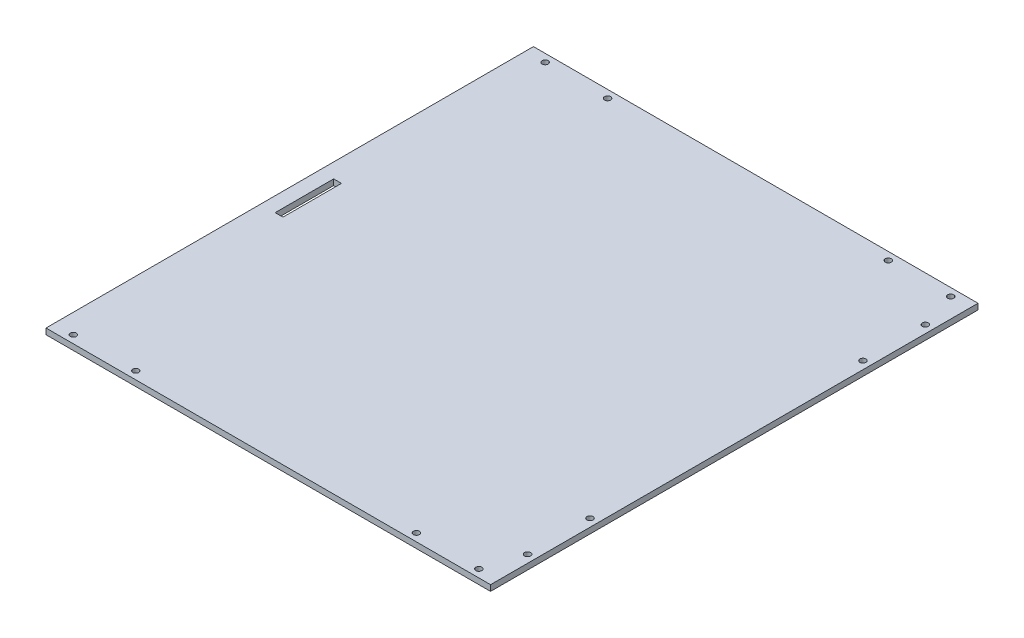
SolidWorks part; units mm, degrees
ref_plane "Front Plane" through (0, 0, 0) normal (0, 0, 1) x (1, 0, 0)
ref_plane "Top Plane" through (0, 0, 0) normal (0, 1, 0) x (1, 0, 0)
ref_plane "Right Plane" through (0, 0, 0) normal (1, 0, 0) x (0, 0, -1)
sketch "Sketch1" plane through (0, 0, 0) normal (0, 1, 0) x (1, 0, 0)
  line L0 (0, 125) -> (228, 125) construction
  line L1 (0, 0) -> (228, 0)
  line L2 (0, 0) -> (0, 250)
  line L3 (0, 250) -> (228, 250)
  line L4 (228, 0) -> (228, 250)
  line L5 (114, 250) -> (114, 0) construction
  line L6 (9.525, 140) -> (9.525, 110) construction
  line L7 (7.525, 140) -> (11.525, 140)
  line L8 (7.525, 140) -> (7.525, 110)
  line L9 (7.525, 110) -> (11.525, 110)
  line L10 (11.525, 140) -> (11.525, 110)
  circle A0 centre (10, 4) radius 1.55
  circle A4 centre (42, 4) radius 1.55
  circle A5 centre (42, 246) radius 1.55
  circle A6 centre (10, 246) radius 1.55
  circle A7 centre (186, 4) radius 1.55
  circle A8 centre (218, 4) radius 1.55
  circle A9 centre (186, 246) radius 1.55
  circle A10 centre (218, 246) radius 1.55
  circle A11 centre (224, 23) radius 1.55
  circle A12 centre (224, 55) radius 1.55
  circle A13 centre (224, 227) radius 1.55
  circle A14 centre (224, 195) radius 1.55
  point P39 (9.525, 125)
  dimension "D3" = 3.1
  dimension "D8" = 3.1
  dimension "D1" = 250
  dimension "D2" = 228
  dimension "D4" = 4
  dimension "D5" = 10
  dimension "D6" = 32
  dimension "D7" = 23
  dimension "D9" = 4
  dimension "D10" = 32
  dimension "D11" = 9.525
  dimension "D12" = 4
  dimension "D13" = 30
extrude "Boss-Extrude1" add sketch "Sketch1" along normal blind 3
equation "\"cf_tube_outer_diameter\"= 25mm"
equation "\"cf_tube_inner_diameter\"= 21mm"
equation "\"mid_plate_mid_to_top\"= 100mm"
equation "\"mid_plate_mid_to_bottom\"= 30mm"
equation "\"mid_plate_horizontal_spacing\"= 250mm"
equation "\"cf_plate_thickness\"= 3mm"
equation "\"mid_tube_length\"= 500mm"
equation "\"mid_plate_bottom_width\"= 180mm"
equation "\"D1@Sketch1\"=\"mid_plate_horizontal_spacing\""
equation "\"mid_support_plate_distance\"= 250mm"
equation "\"D1@Boss-Extrude1\"=\"cf_plate_thickness\""
equation "\"nut_strip_2_hole_distance\"= 7mm"
equation "\"nut_strip_hole_diameter\"= 2.5mm"
equation "\"nut_strip_hole_to_edge_distance\"= 2.5mm"
equation "\"M3_screw_hole_diameter\"= 3.1mm"
equation "\"D3@Sketch1\"=\"M3_screw_hole_diameter\""
equation "\"D8@Sketch1\"=\"M3_screw_hole_diameter\""
